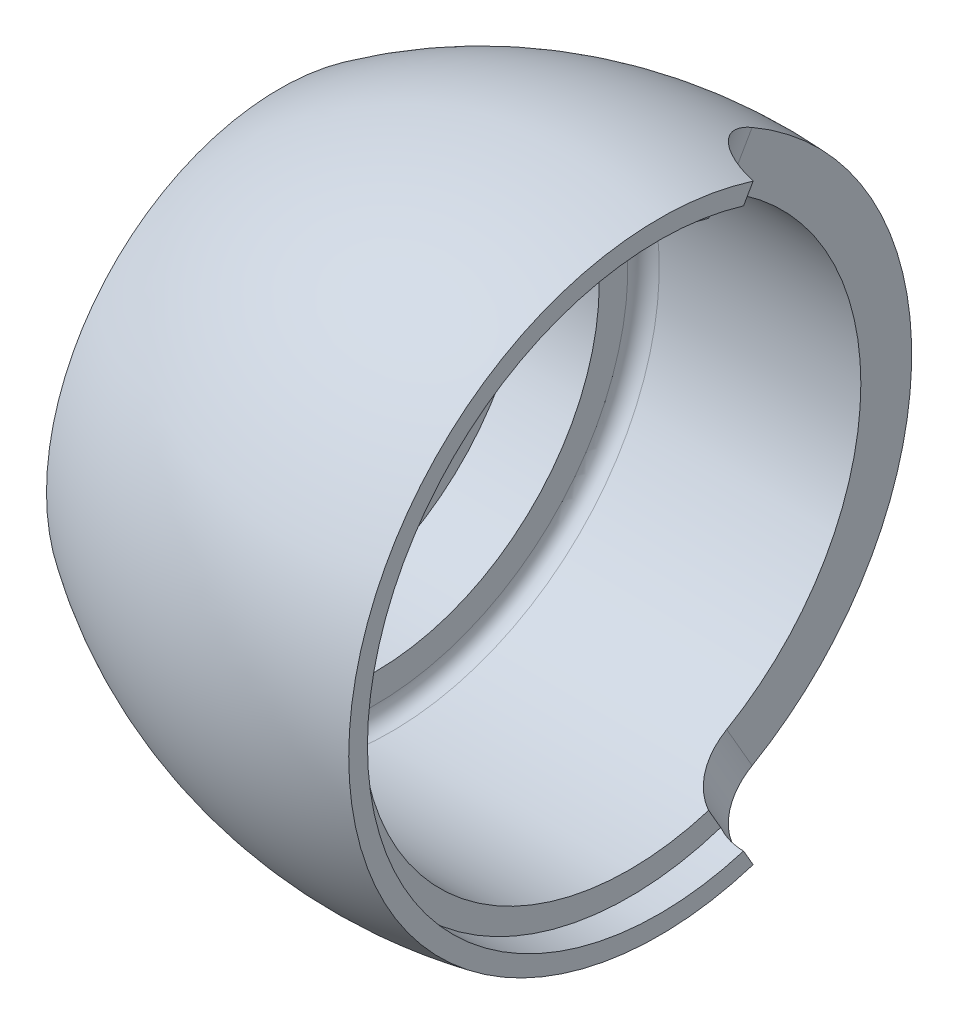
SolidWorks part; units mm, degrees
ref_plane "Front Plane" through (0, 0, 0) normal (0, 0, 1) x (1, 0, 0)
ref_plane "Top Plane" through (0, 0, 0) normal (0, 1, 0) x (1, 0, 0)
ref_plane "Right Plane" through (0, 0, 0) normal (1, 0, 0) x (0, 0, -1)
sketch "Sketch1" plane through (0, 0, 0) normal (0, 0, 1) x (1, 0, 0)
  line L0 (0, -55) -> (0, 55) construction
  line L1 (55, 0) -> (-55, 0) construction
  line L3 (-38.608, 0) -> (-38.608, 22.86)
  line L4 (-38.608, 22.86) -> (-41.91, 22.86)
  line L5 (-41.91, 31.75) -> (-41.91, 36.2585)
  line L7 (-42.418, 0) -> (-38.608, 0)
  line L9 (-30.226, 36.2585) -> (-41.91, 36.2585)
  line L10 (-45.72, 37.7381) -> (-45.72, 19.05)
  line L14 (-30.226, 43.434) -> (10.948, 43.434)
  line L17 (-45.72, 19.05) -> (-42.418, 19.05)
  line L18 (-42.418, 19.05) -> (-42.418, 0)
  line L19 (-41.91, 31.75) -> (-42.21, 31.75)
  line L20 (-42.21, 31.75) -> (-42.21, 22.86)
  line L21 (-42.21, 22.86) -> (-41.91, 22.86)
  line L22 (-30.226, 36.2585) -> (-30.226, 43.434)
  line L23 (15.748, 50.2758) -> (15.748, 47.244)
  line L24 (15.748, 47.244) -> (10.948, 47.244)
  line L25 (10.948, 47.244) -> (10.948, 43.434)
  arc A1 (15.748, 50.2758) -> (-45.72, 37.7381) centre (0, -29.464) ccw
  dimension "D1" = 81.28
  dimension "D2" = 43.434
  dimension "D3" = 45.72
  dimension "D4" = 22.86
  dimension "D5" = 7.112
  dimension "D6" = 11.684
  dimension "D7" = 29.464
  dimension "D8" = 3.81
  dimension "D9" = 36.2585
  dimension "D10" = 4.8
  dimension "D11" = 15.748
  dimension "D12" = 3.81
  dimension "D13" = 3.81
  dimension "D14" = 0.3
  dimension "D15" = 8.89
  dimension "D16" = 3.81
revolve "Revolve1" add sketch "Sketch1" angle 360 about L7
fillet "Fillet1" radius 2.54 1 edges at (-30.226, 0, 43.434)
sketch "Sketch2" plane through (0, 0, 0) normal (0, 1, 0) x (1, 0, 0)
  line L0 (-45.72, 37.7381) -> (-45.72, -37.7381) construction
  line L1 (15.748, 55.0051) -> (63.4741, 55.0051)
  line L2 (15.748, 55.0051) -> (15.748, 38.4582)
  line L3 (15.748, 38.4582) -> (63.4741, 38.4582)
  line L4 (63.4741, 55.0051) -> (63.4741, 38.4582)
  line L5 (-43.7615, 0) -> (38.5109, 0) construction
  line L6 (-56.9976, 0) -> (56.9976, 0) construction
  dimension "D1" = 61.468
ref_axis "Axis1" through (-48.7934, 0, 0) along (1, 0, 0)
ref_plane "Plane3" through (0, 0, 0) normal (0, -0.866, 0.5) x (1, 0, 0)
sketch "Sketch9" plane through (0, 0, 0) normal (0, -0.866, 0.5) x (1, 0, 0)
  line L0 (-48.7934, 0) -> (18.8214, 0) construction
  line L1 (15.748, -47.244) -> (15.748, 47.244) construction
  circle A0 centre (15.748, 0) radius 10.795
  dimension "D1" = 21.59
extrude "Cut-Extrude4" cut sketch "Sketch9" against normal blind 57.912
mirror "Mirror3" about plane through (0, 0, 0) normal (0, 1, 0) of "Cut-Extrude4"
ref_plane "Plane4" through (0, 0, 0) normal (0, -0.5, -0.866) x (1, 0, 0)
sketch "Sketch10" plane through (0, 0, 0) normal (0, -0.5, -0.866) x (1, 0, 0)
  line L0 (4.953, -43.434) -> (4.953, -51.6649) construction
  line L1 (4.953, -36.5537) -> (34.3932, -36.5537)
  line L2 (4.953, -36.5537) -> (4.953, -56.7179)
  line L3 (4.953, -56.7179) -> (34.3932, -56.7179)
  line L4 (34.3932, -36.5537) -> (34.3932, -56.7179)
revolve "Cut-Revolve2" cut sketch "Sketch10" angle 120 about axis through (-48.7934, 0, 0) along (1, 0, 0) reverse direction yes
